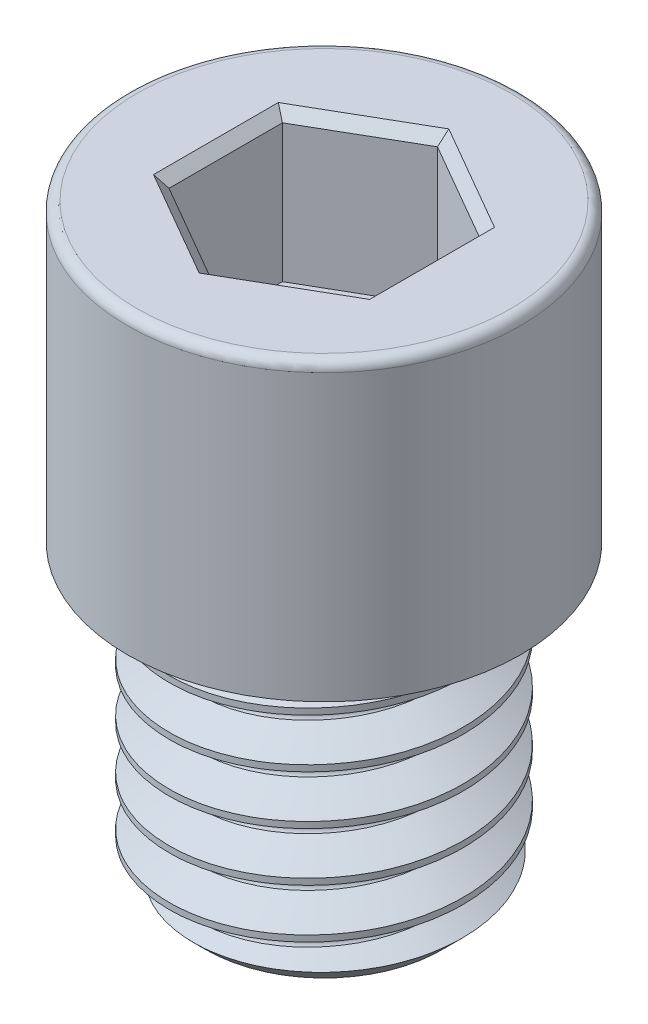
SolidWorks part; units mm, degrees
ref_plane "Ebene vorne" through (0, 0, 0) normal (0, 0, 1) x (1, 0, 0)
ref_plane "Ebene oben" through (0, 0, 0) normal (0, 1, 0) x (1, 0, 0)
ref_plane "Ebene rechts" through (0, 0, 0) normal (1, 0, 0) x (0, 0, -1)
sketch "Sketch1" plane through (0, 0, 0) normal (0, 0, 1) x (1, 0, 0)
  line L0 (-14.6254, 0) -> (16.6081, 0) construction
  line L1 (0, 0) -> (0, 2)
  line L2 (0, 2) -> (3, 2)
  line L3 (3, 2) -> (3, 1.5)
  line L4 (3, 1.5) -> (6, 1.5)
  line L5 (6, 1.5) -> (6, 0)
  line L6 (0, 0) -> (6, 0)
  dimension "D1" = 1.5
  dimension "D2" = 3
  dimension "D3" = 2
  dimension "D4" = 3
other "AlignGroup1"
other "AlignGroup2"
other "AlignGroup3"
revolve "Revolve1" add sketch "Sketch1" angle 360 about L0
sketch "Sketch3" plane through (3, 0, 0) normal (1, 0, 0) x (0, 0, -1)
  circle A0 centre (0, 0) radius 1.5
curve "Helix/Spiral1" pitch 0.5 height 11 radius 1.5 centre (3, 0, 0) axis (1, 0, 0) start towards (0, 0, -1)
sketch "Sketch4" plane through (0, 0, 0) normal (0, 1, 0) x (1, 0, 0)
  line L0 (-6.0413, 0) -> (11.0618, 0) construction
  line L1 (-6.0413, 1.5) -> (11.0618, 1.5) construction
  dimension "D1" = 1.5
chamfer "Chamfer1" distance 0.3 angle 45 1 edges at (6, 0, 1.5)
sketch "Sketch5" plane through (0, 0, 0) normal (0, 1, 0) x (1, 0, 0)
  line L0 (4.5877, 1.3375) -> (3.435, 1.3375) construction
  line L1 (-6.0413, 0) -> (11.0618, 0) construction
  line L2 (2.75, 1.6191) -> (2.75, 0.9933) construction
  line L3 (2.5, 1.5889) -> (2.5, 0.9756) construction
  line L4 (2.7812, 1.5) -> (2.9582, 1.1935)
  line L5 (2.7188, 1.5) -> (2.5418, 1.1935)
  line L6 (-6.0413, 1.5) -> (11.0618, 1.5) construction
  line L7 (3.6285, 1.1935) -> (3.4482, 1.1935) construction
  line L8 (3, 1.5889) -> (3, 0.9756) construction
  line L9 (2.7188, 1.5) -> (2.7812, 1.5)
  line L10 (2.5, 1.1774) -> (3.2169, 1.1774)
  line L11 (2.75, 1.5541) -> (3, 1.1211) construction
  line L13 (2.75, 1.5541) -> (2.5, 1.1208) construction
  line L14 (3, -2) -> (3, 2) construction
  line L15 (3.2188, 1.5) -> (3.0418, 1.1935)
  line L16 (2.7812, 1.5) -> (3.2188, 1.5)
  arc A1 (2.9582, 1.1935) -> (3.0418, 1.1935) centre (3, 1.2395) ccw
  arc A2 (2.5418, 1.1935) -> (2.5, 1.1774) centre (2.5, 1.2395) cw
  spline S0 degree 3 poles (3, 1.5) (3.0104, 1.5) (3.0313, 1.4219) (3.0625, 1.0883) (3.1042, 0.4225) (3.1458, -0.4225) (3.1875, -1.0883) (3.2188, -1.4219) (3.25, -1.5391) (3.2813, -1.4219) (3.3125, -1.0883) (3.3542, -0.4225) (3.3958, 0.4225) (3.4375, 1.0883) (3.4688, 1.4219) (3.5, 1.5391) (3.5313, 1.4219) (3.5625, 1.0883) (3.6042, 0.4225) (3.6458, -0.4225) (3.6875, -1.0883) (3.7188, -1.4219) (3.75, -1.5391) (3.7812, -1.4219) (3.8125, -1.0883) (3.8542, -0.4225) (3.8958, 0.4225) (3.9375, 1.0883) (3.9688, 1.4219) (4, 1.5391) (4.0313, 1.4219) (4.0625, 1.0883) (4.1042, 0.4225) (4.1458, -0.4225) (4.1875, -1.0883) (4.2188, -1.4219) (4.25, -1.5391) (4.2813, -1.4219) (4.3125, -1.0883) (4.3542, -0.4225) (4.3958, 0.4225) (4.4375, 1.0883) (4.4688, 1.4219) (4.5, 1.5391) (4.5313, 1.4219) (4.5625, 1.0883) (4.6042, 0.4225) (4.6458, -0.4225) (4.6875, -1.0883) (4.7188, -1.4219) (4.75, -1.5391) (4.7813, -1.4219) (4.8125, -1.0883) (4.8542, -0.4225) (4.8958, 0.4225) (4.9375, 1.0883) (4.9688, 1.4219) (5, 1.5391) (5.0313, 1.4219) (5.0625, 1.0883) (5.1042, 0.4225) (5.1458, -0.4225) (5.1875, -1.0883) (5.2188, -1.4219) (5.25, -1.5391) (5.2813, -1.4219) (5.3125, -1.0883) (5.3542, -0.4225) (5.3958, 0.4225) (5.4375, 1.0883) (5.4688, 1.4219) (5.5, 1.5391) (5.5313, 1.4219) (5.5625, 1.0883) (5.6042, 0.4225) (5.6458, -0.4225) (5.6875, -1.0883) (5.7188, -1.4219) (5.75, -1.5391) (5.7813, -1.4219) (5.8125, -1.0883) (5.8542, -0.4225) (5.8958, 0.4225) (5.9375, 1.0883) (5.9688, 1.4219) (6, 1.5391) (6.0313, 1.4219) (6.0625, 1.0883) (6.1042, 0.4225) (6.1458, -0.4225) (6.1875, -1.0883) (6.2188, -1.4219) (6.25, -1.5391) (6.2812, -1.4219) (6.3125, -1.0883) (6.3542, -0.4225) (6.3958, 0.4225) (6.4375, 1.0883) (6.4688, 1.4219) (6.5, 1.5391) (6.5313, 1.4219) (6.5625, 1.0883) (6.6042, 0.4225) (6.6458, -0.4225) (6.6875, -1.0883) (6.7188, -1.4219) (6.75, -1.5391) (6.7813, -1.4219) (6.8125, -1.0883) (6.8542, -0.4225) (6.8958, 0.4225) (6.9375, 1.0883) (6.9688, 1.4219) (7, 1.5391) (7.0313, 1.4219) (7.0625, 1.0883) (7.1042, 0.4225) (7.1458, -0.4225) (7.1875, -1.0883) (7.2188, -1.4219) (7.25, -1.5391) (7.2813, -1.4219) (7.3125, -1.0883) (7.3542, -0.4225) (7.3958, 0.4225) (7.4375, 1.0883) (7.4688, 1.4219) (7.5, 1.5391) (7.5313, 1.4219) (7.5625, 1.0883) (7.6042, 0.4225) (7.6458, -0.4225) (7.6875, -1.0883) (7.7188, -1.4219) (7.75, -1.5391) (7.7813, -1.4219) (7.8125, -1.0883) (7.8542, -0.4225) (7.8958, 0.4225) (7.9375, 1.0883) (7.9688, 1.4219) (8, 1.5391) (8.0313, 1.4219) (8.0625, 1.0883) (8.1042, 0.4225) (8.1458, -0.4225) (8.1875, -1.0883) (8.2188, -1.4219) (8.25, -1.5391) (8.2813, -1.4219) (8.3125, -1.0883) (8.3542, -0.4225) (8.3958, 0.4225) (8.4375, 1.0883) (8.4688, 1.4219) (8.5, 1.5391) (8.5313, 1.4219) (8.5625, 1.0883) (8.6042, 0.4225) (8.6458, -0.4225) (8.6875, -1.0883) (8.7188, -1.4219) (8.75, -1.5391) (8.7813, -1.4219) (8.8125, -1.0883) (8.8542, -0.4225) (8.8958, 0.4225) (8.9375, 1.0883) (8.9688, 1.4219) (9, 1.5391) (9.0313, 1.4219) (9.0625, 1.0883) (9.1042, 0.4225) (9.1458, -0.4225) (9.1875, -1.0883) (9.2188, -1.4219) (9.25, -1.5391) (9.2813, -1.4219) (9.3125, -1.0883) (9.3542, -0.4225) (9.3958, 0.4225) (9.4375, 1.0883) (9.4688, 1.4219) (9.5, 1.5391) (9.5313, 1.4219) (9.5625, 1.0883) (9.6042, 0.4225) (9.6458, -0.4225) (9.6875, -1.0883) (9.7188, -1.4219) (9.75, -1.5391) (9.7813, -1.4219) (9.8125, -1.0883) (9.8542, -0.4225) (9.8958, 0.4225) (9.9375, 1.0883) (9.9688, 1.4219) (10, 1.5391) (10.0313, 1.4219) (10.0625, 1.0883) (10.1042, 0.4225) (10.1458, -0.4225) (10.1875, -1.0883) (10.2188, -1.4219) (10.25, -1.5391) (10.2813, -1.4219) (10.3125, -1.0883) (10.3542, -0.4225) (10.3958, 0.4225) (10.4375, 1.0883) (10.4688, 1.4219) (10.5, 1.5391) (10.5313, 1.4219) (10.5625, 1.0883) (10.6042, 0.4225) (10.6458, -0.4225) (10.6875, -1.0883) (10.7188, -1.4219) (10.75, -1.5391) (10.7813, -1.4219) (10.8125, -1.0883) (10.8542, -0.4225) (10.8958, 0.4225) (10.9375, 1.0883) (10.9688, 1.4219) (11, 1.5391) (11.0313, 1.4219) (11.0625, 1.0883) (11.1042, 0.4225) (11.1458, -0.4225) (11.1875, -1.0883) (11.2188, -1.4219) (11.25, -1.5391) (11.2813, -1.4219) (11.3125, -1.0883) (11.3542, -0.4225) (11.3958, 0.4225) (11.4375, 1.0883) (11.4688, 1.4219) (11.5, 1.5391) (11.5313, 1.4219) (11.5625, 1.0883) (11.6042, 0.4225) (11.6458, -0.4225) (11.6875, -1.0883) (11.7188, -1.4219) (11.75, -1.5391) (11.7813, -1.4219) (11.8125, -1.0883) (11.8542, -0.4225) (11.8958, 0.4225) (11.9375, 1.0883) (11.9688, 1.4219) (12, 1.5391) (12.0313, 1.4219) (12.0625, 1.0883) (12.1042, 0.4225) (12.1458, -0.4225) (12.1875, -1.0883) (12.2188, -1.4219) (12.25, -1.5391) (12.2813, -1.4219) (12.3125, -1.0883) (12.3542, -0.4225) (12.3958, 0.4225) (12.4375, 1.0883) (12.4688, 1.4219) (12.5, 1.5391) (12.5313, 1.4219) (12.5625, 1.0883) (12.6042, 0.4225) (12.6458, -0.4225) (12.6875, -1.0883) (12.7188, -1.4219) (12.75, -1.5391) (12.7813, -1.4219) (12.8125, -1.0883) (12.8542, -0.4225) (12.8958, 0.4225) (12.9375, 1.0883) (12.9688, 1.4219) (13, 1.5391) (13.0313, 1.4219) (13.0625, 1.0883) (13.1042, 0.4225) (13.1458, -0.4225) (13.1875, -1.0883) (13.2188, -1.4219) (13.25, -1.5391) (13.2813, -1.4219) (13.3125, -1.0883) (13.3542, -0.4225) (13.3958, 0.4225) (13.4375, 1.0883) (13.4687, 1.4219) (13.5, 1.5391) (13.5312, 1.4219) (13.5625, 1.0883) (13.6042, 0.4225) (13.6458, -0.4225) (13.6875, -1.0883) (13.7187, -1.4219) (13.75, -1.5391) (13.7812, -1.4219) (13.8125, -1.0883) (13.8542, -0.4225) (13.8958, 0.4225) (13.9375, 1.0883) (13.9687, 1.4219) (13.9896, 1.5) (14, 1.5) knots 0 0 0 0 0.002841 0.005682 0.008523 0.014205 0.017045 0.019886 0.022727 0.025568 0.028409 0.03125 0.036932 0.039773 0.042614 0.045455 0.048295 0.051136 0.053977 0.059659 0.0625 0.065341 0.068182 0.071023 0.073864 0.076705 0.082386 0.085227 0.088068 0.090909 0.09375 0.096591 0.099432 0.105114 0.107955 0.110795 0.113636 0.116477 0.119318 0.122159 0.127841 0.130682 0.133523 0.136364 0.139205 0.142045 0.144886 0.150568 0.153409 0.15625 0.159091 0.161932 0.164773 0.167614 0.173295 0.176136 0.178977 0.181818 0.184659 0.1875 0.190341 0.196023 0.198864 0.201705 0.204545 0.207386 0.210227 0.213068 0.21875 0.221591 0.224432 0.227273 0.230114 0.232955 0.235795 0.241477 0.244318 0.247159 0.25 0.252841 0.255682 0.258523 0.264205 0.267045 0.269886 0.272727 0.275568 0.278409 0.28125 0.286932 0.289773 0.292614 0.295455 0.298295 0.301136 0.303977 0.309659 0.3125 0.315341 0.318182 0.321023 0.323864 0.326705 0.332386 0.335227 0.338068 0.340909 0.34375 0.346591 0.349432 0.355114 0.357955 0.360795 0.363636 0.366477 0.369318 0.372159 0.377841 0.380682 0.383523 0.386364 0.389205 0.392045 0.394886 0.400568 0.403409 0.40625 0.409091 0.411932 0.414773 0.417614 0.423295 0.426136 0.428977 0.431818 0.434659 0.4375 0.440341 0.446023 0.448864 0.451705 0.454545 0.457386 0.460227 0.463068 0.46875 0.471591 0.474432 0.477273 0.480114 0.482955 0.485795 0.491477 0.494318 0.497159 0.5 0.502841 0.505682 0.508523 0.514205 0.517045 0.519886 0.522727 0.525568 0.528409 0.53125 0.536932 0.539773 0.542614 0.545455 0.548295 0.551136 0.553977 0.559659 0.5625 0.565341 0.568182 0.571023 0.573864 0.576705 0.582386 0.585227 0.588068 0.590909 0.59375 0.596591 0.599432 0.605114 0.607955 0.610795 0.613636 0.616477 0.619318 0.622159 0.627841 0.630682 0.633523 0.636364 0.639205 0.642045 0.644886 0.650568 0.653409 0.65625 0.659091 0.661932 0.664773 0.667614 0.673295 0.676136 0.678977 0.681818 0.684659 0.6875 0.690341 0.696023 0.698864 0.701705 0.704545 0.707386 0.710227 0.713068 0.71875 0.721591 0.724432 0.727273 0.730114 0.732955 0.735795 0.741477 0.744318 0.747159 0.75 0.752841 0.755682 0.758523 0.764205 0.767045 0.769886 0.772727 0.775568 0.778409 0.78125 0.786932 0.789773 0.792614 0.795455 0.798295 0.801136 0.803977 0.809659 0.8125 0.815341 0.818182 0.821023 0.823864 0.826705 0.832386 0.835227 0.838068 0.840909 0.84375 0.846591 0.849432 0.855114 0.857955 0.860795 0.863636 0.866477 0.869318 0.872159 0.877841 0.880682 0.883523 0.886364 0.889205 0.892045 0.894886 0.900568 0.903409 0.90625 0.909091 0.911932 0.914773 0.917614 0.923295 0.926136 0.928977 0.931818 0.934659 0.9375 0.940341 0.946023 0.948864 0.951705 0.954545 0.957386 0.960227 0.963068 0.96875 0.971591 0.974432 0.977273 0.980114 0.982955 0.985795 0.991477 0.994318 0.997159 1 1 1 1 construction
  dimension "D8" = 0
  dimension "D2" = 0.5
  dimension "D4" = 0.0541
  dimension "D6" = 0.0161
  dimension "D1" = 1.3375
  dimension "D3" = 60
  dimension "D5" = 0.25
  dimension "D7" = 1.1935
sweep "Cut-Sweep2" cut profiles "Sketch5" path "Helix/Spiral1" align with end faces yes
sketch "Sketch6" plane through (0, 0, 0) normal (-1, 0, 0) x (0, 0, 1)
  line L0 (0.5774, 1) -> (-0.5774, 1)
  line L1 (-0.5774, 1) -> (-1.1547, 0)
  line L2 (-1.1547, 0) -> (-0.5774, -1)
  line L3 (-0.5774, -1) -> (0.5774, -1)
  line L4 (0.5774, -1) -> (1.1547, 0)
  line L5 (1.1547, 0) -> (0.5774, 1)
  line L6 (-0.5774, -1) -> (0.5774, 1) construction
  line L7 (-0.5774, 1) -> (0.5774, -1) construction
  point P6 (0, 0)
  dimension "D1" = 2
  dimension "D2" = 2
  dimension "D3" = 0
  dimension "D4" = 2
extrude "Cut-Extrude1" cut sketch "Sketch6" against normal blind 1.5
chamfer "Chamfer2" distance 0.1 angle 45 6 edges at (0, 0.5, -0.866) (0, -0.5, -0.866) (0, -1, 0) (0, -0.5, 0.866) (0, 0.5, 0.866) (0, 1, 0)
fillet "Fillet1" radius 0.1 1 edges at (0, 0, 2)
move or copy body "Body-Move/Copy1" bodies to move or copy 103 copy no rotation origin (6.6185, 0, 0) rotation axis (0, 0, -1) rotation angle 90
